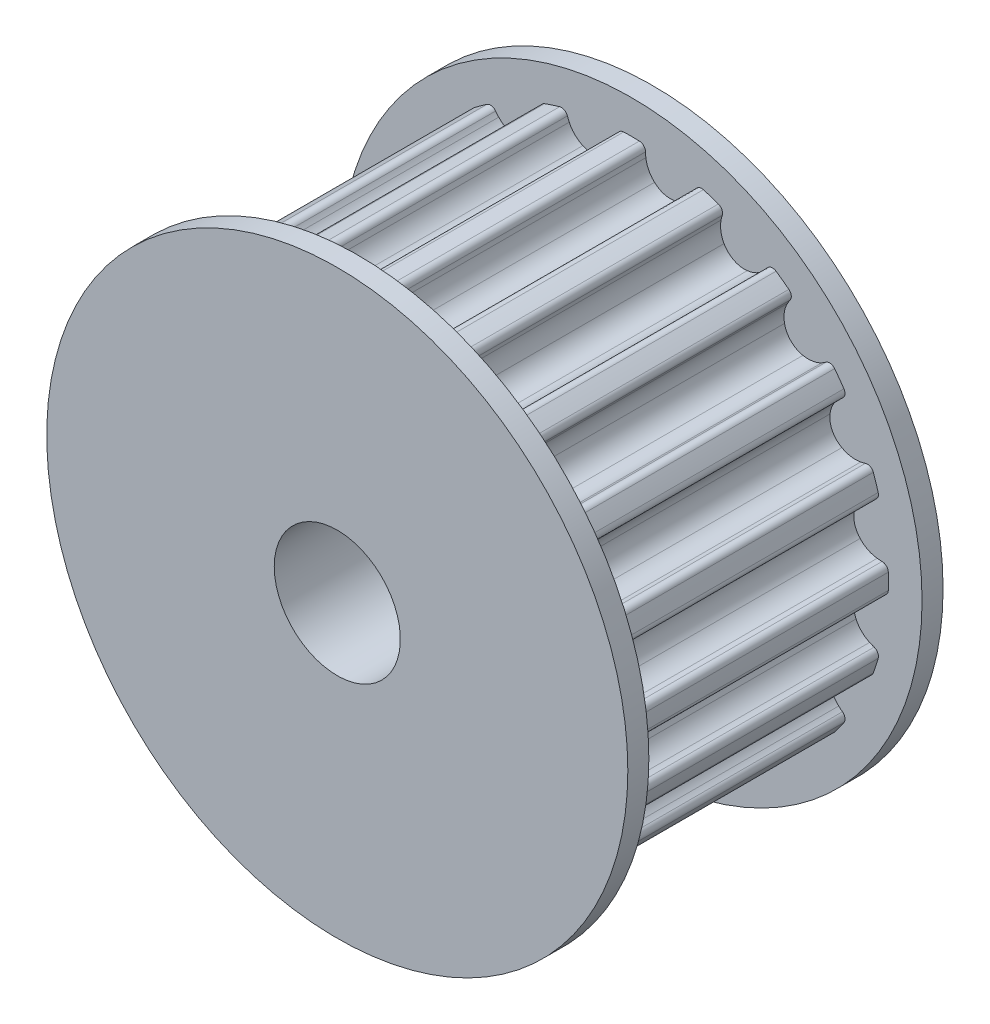
SolidWorks part; units mm, degrees
material "PET"
ref_plane "Front Plane" through (0, 0, 0) normal (0, 0, 1) x (1, 0, 0)
ref_plane "Top Plane" through (0, 0, 0) normal (0, 1, 0) x (1, 0, 0)
ref_plane "Right Plane" through (0, 0, 0) normal (1, 0, 0) x (0, 0, -1)
sketch "Sketch1" plane through (0, 0, 0) normal (0, 0, 1) x (1, 0, 0)
  line L0 (0, 0) -> (0, 6.3662) construction
  line L1 (0, 0) -> (0.9959, 6.2878) construction
  line L2 (0, 0) -> (1.3887, 6.2129) construction
  circle A0 centre (0, 0) radius 6.3662 construction
  circle A1 centre (0, 0) radius 5.3622 construction
  circle A2 centre (0, 0) radius 6.1122 construction
  arc A3 (0.8388, 5.2962) -> (0.5472, 5.4384) centre (0.9257, 5.8443) cw
  arc A4 (0.3406, 5.8443) -> (0.3333, 5.9601) centre (1.3333, 5.965) cw
  circle A5 centre (0, 0) radius 5.9622 construction
  arc A6 (-0.188, 6.1093) -> (0.188, 6.1093) centre (0, 0) cw
  arc A7 (0.188, 6.1093) -> (0.3333, 5.9601) centre (0.1833, 5.9594) cw
  arc A8 (0.3406, 5.8443) -> (0.5472, 5.4384) centre (1.0004, 5.9245) ccw
  arc A9 (-0.8388, 5.2962) -> (-0.5472, 5.4384) centre (-0.9257, 5.8443) ccw
  arc A10 (-0.3406, 5.8443) -> (-0.5472, 5.4384) centre (-1.0004, 5.9245) cw
  arc A11 (-0.3406, 5.8443) -> (-0.3333, 5.9601) centre (-1.3333, 5.965) ccw
  arc A12 (-0.188, 6.1093) -> (-0.3333, 5.9601) centre (-0.1833, 5.9594) ccw
  arc A13 (-0.8388, 5.2962) -> (0.8388, 5.2962) centre (0, 0) cw
  dimension "D1" = 12.7324
  dimension "D6" = 0.555
  dimension "D7" = 1
  dimension "D9" = 0.15
  dimension "D2" = 9
  dimension "D3" = 3.6
  dimension "D4" = 1.004
  dimension "D5" = 0.75
  dimension "D8" = 0.15
extrude "Boss-Extrude1" add sketch "Sketch1" along normal blind 6.5
ref_axis "Axis1" through (0, 0, -0.375) along (0, 0, 1)
pattern_circular "CirPattern1" count 20 over 360 about axis through (0, 0, -0.375) along (0, 0, 1) of bodies 107
sketch "Sketch2" plane through (0, 0, 0) normal (0, 0, -1) x (-1, 0, 0)
  circle A0 centre (0, 0) radius 5.3622
  arc A1 (0.8388, 5.2962) -> (-0.8388, 5.2962) centre (0, 0) ccw construction
extrude "Boss-Extrude2" add sketch "Sketch2" against normal up to surface (6.5 mm away)
sketch "Schizzo1" plane through (0, 0, 6.5) normal (0, 0, 1) x (1, 0, 0)
  circle A0 centre (0, 0) radius 6.9122
  arc A1 (-6.1093, 0.188) -> (-6.1093, -0.188) centre (0, 0) ccw construction
  dimension "D1" = 0.8
extrude "Estrusione-Estrusione1" add sketch "Schizzo1" along normal blind 0.5
ref_plane "Piano1" through (0, 0, 3.25) normal (0, 0, -1) x (-1, 0, 0)
mirror "Specchia1" about plane through (0, 0, 3.25) normal (0, 0, -1) of "Estrusione-Estrusione1"
sketch "Schizzo3" plane through (0, 0, -0.5) normal (0, 0, -1) x (-1, 0, 0)
  circle A0 centre (0, 0) radius 1.5
  dimension "D1" = 3
extrude "Taglio-Estrusione2" cut sketch "Schizzo3" against normal through all
sketch "Schizzo2" plane through (0, 0, -0.5) normal (0, 0, -1) x (-1, 0, 0)
  arc A0 (-0.1172, 3.5721) -> (-0.645, 4.6555) centre (-1.906, 3.3711) ccw
  arc A1 (0.1172, 3.5721) -> (-0.1172, 3.5721) centre (0, 0) ccw
  arc A2 (0.645, 4.6555) -> (0.1172, 3.5721) centre (1.906, 3.3711) ccw
  arc A3 (1.1857, 4.548) -> (0.645, 4.6555) centre (0, 0) ccw
  arc A4 (1.2587, 3.345) -> (1.1857, 4.548) centre (-0.4708, 3.8439) ccw
  arc A5 (1.4753, 3.2553) -> (1.2587, 3.345) centre (0, 0) ccw
  arc A6 (2.3775, 4.0543) -> (1.4753, 3.2553) centre (3.051, 2.3851) ccw
  arc A7 (2.8359, 3.748) -> (2.3775, 4.0543) centre (0, 0) ccw
  arc A8 (2.4429, 2.6087) -> (2.8359, 3.748) centre (1.036, 3.7314) ccw
  arc A9 (2.6087, 2.4429) -> (2.4429, 2.6087) centre (0, 0) ccw
  arc A10 (3.748, 2.8359) -> (2.6087, 2.4429) centre (3.7314, 1.036) ccw
  arc A11 (4.0543, 2.3775) -> (3.748, 2.8359) centre (0, 0) ccw
  arc A12 (3.2553, 1.4753) -> (4.0543, 2.3775) centre (2.3851, 3.051) ccw
  arc A13 (3.345, 1.2587) -> (3.2553, 1.4753) centre (0, 0) ccw
  arc A14 (4.548, 1.1857) -> (3.345, 1.2587) centre (3.8439, -0.4708) ccw
  arc A15 (4.6555, 0.645) -> (4.548, 1.1857) centre (0, 0) ccw
  arc A16 (3.5721, 0.1172) -> (4.6555, 0.645) centre (3.3711, 1.906) ccw
  arc A17 (3.5721, -0.1172) -> (3.5721, 0.1172) centre (0, 0) ccw
  arc A18 (4.6555, -0.645) -> (3.5721, -0.1172) centre (3.3711, -1.906) ccw
  arc A19 (4.548, -1.1857) -> (4.6555, -0.645) centre (0, 0) ccw
  arc A20 (3.345, -1.2587) -> (4.548, -1.1857) centre (3.8439, 0.4708) ccw
  arc A21 (3.2553, -1.4753) -> (3.345, -1.2587) centre (0, 0) ccw
  arc A22 (4.0543, -2.3775) -> (3.2553, -1.4753) centre (2.3851, -3.051) ccw
  arc A23 (3.748, -2.8359) -> (4.0543, -2.3775) centre (0, 0) ccw
  arc A24 (2.6087, -2.4429) -> (3.748, -2.8359) centre (3.7314, -1.036) ccw
  arc A25 (2.4429, -2.6087) -> (2.6087, -2.4429) centre (0, 0) ccw
  arc A26 (2.8359, -3.748) -> (2.4429, -2.6087) centre (1.036, -3.7314) ccw
  arc A27 (2.3775, -4.0543) -> (2.8359, -3.748) centre (0, 0) ccw
  arc A28 (1.4753, -3.2553) -> (2.3775, -4.0543) centre (3.051, -2.3851) ccw
  arc A29 (1.2587, -3.345) -> (1.4753, -3.2553) centre (0, 0) ccw
  arc A30 (1.1857, -4.548) -> (1.2587, -3.345) centre (-0.4708, -3.8439) ccw
  arc A31 (0.645, -4.6555) -> (1.1857, -4.548) centre (0, 0) ccw
  arc A32 (0.1172, -3.5721) -> (0.645, -4.6555) centre (1.906, -3.3711) ccw
  arc A33 (-0.1172, -3.5721) -> (0.1172, -3.5721) centre (0, 0) ccw
  arc A34 (-0.645, -4.6555) -> (-0.1172, -3.5721) centre (-1.906, -3.3711) ccw
  arc A35 (-1.1857, -4.548) -> (-0.645, -4.6555) centre (0, 0) ccw
  arc A36 (-1.2587, -3.345) -> (-1.1857, -4.548) centre (0.4708, -3.8439) ccw
  arc A37 (-1.4753, -3.2553) -> (-1.2587, -3.345) centre (0, 0) ccw
  arc A38 (-2.3775, -4.0543) -> (-1.4753, -3.2553) centre (-3.051, -2.3851) ccw
  arc A39 (-2.8359, -3.748) -> (-2.3775, -4.0543) centre (0, 0) ccw
  arc A40 (-2.4429, -2.6087) -> (-2.8359, -3.748) centre (-1.036, -3.7314) ccw
  arc A41 (-2.6087, -2.4429) -> (-2.4429, -2.6087) centre (0, 0) ccw
  arc A42 (-3.748, -2.8359) -> (-2.6087, -2.4429) centre (-3.7314, -1.036) ccw
  arc A43 (-4.0543, -2.3775) -> (-3.748, -2.8359) centre (0, 0) ccw
  arc A44 (-3.2553, -1.4753) -> (-4.0543, -2.3775) centre (-2.3851, -3.051) ccw
  arc A45 (-3.345, -1.2587) -> (-3.2553, -1.4753) centre (0, 0) ccw
  arc A46 (-4.548, -1.1857) -> (-3.345, -1.2587) centre (-3.8439, 0.4708) ccw
  arc A47 (-4.6555, -0.645) -> (-4.548, -1.1857) centre (0, 0) ccw
  arc A48 (-3.5721, -0.1172) -> (-4.6555, -0.645) centre (-3.3711, -1.906) ccw
  arc A49 (-3.5721, 0.1172) -> (-3.5721, -0.1172) centre (0, 0) ccw
  arc A50 (-4.6555, 0.645) -> (-3.5721, 0.1172) centre (-3.3711, 1.906) ccw
  arc A51 (-4.548, 1.1857) -> (-4.6555, 0.645) centre (0, 0) ccw
  arc A52 (-3.345, 1.2587) -> (-4.548, 1.1857) centre (-3.8439, -0.4708) ccw
  arc A53 (-3.2553, 1.4753) -> (-3.345, 1.2587) centre (0, 0) ccw
  arc A54 (-4.0543, 2.3775) -> (-3.2553, 1.4753) centre (-2.3851, 3.051) ccw
  arc A55 (-3.748, 2.8359) -> (-4.0543, 2.3775) centre (0, 0) ccw
  arc A56 (-2.6087, 2.4429) -> (-3.748, 2.8359) centre (-3.7314, 1.036) ccw
  arc A57 (-2.4429, 2.6087) -> (-2.6087, 2.4429) centre (0, 0) ccw
  arc A58 (-2.8359, 3.748) -> (-2.4429, 2.6087) centre (-1.036, 3.7314) ccw
  arc A59 (-2.3775, 4.0543) -> (-2.8359, 3.748) centre (0, 0) ccw
  arc A60 (-1.4753, 3.2553) -> (-2.3775, 4.0543) centre (-3.051, 2.3851) ccw
  arc A61 (-1.2587, 3.345) -> (-1.4753, 3.2553) centre (0, 0) ccw
  arc A62 (-1.1857, 4.548) -> (-1.2587, 3.345) centre (0.4708, 3.8439) ccw
  arc A63 (-0.645, 4.6555) -> (-1.1857, 4.548) centre (0, 0) ccw
  arc A64 (-0.2087, 3.4677) -> (-0.6806, 4.5494) centre (-1.906, 3.3711) ccw
  arc A65 (-0.6806, 4.5494) -> (-1.1122, 4.4635) centre (0, 0) ccw
  arc A66 (-1.1122, 4.4635) -> (-1.1342, 3.2836) centre (0.4708, 3.8439) ccw
  arc A67 (-1.1342, 3.2836) -> (-1.5199, 3.1239) centre (0, 0) ccw
  arc A68 (-1.5199, 3.1239) -> (-2.3697, 3.9426) centre (-3.051, 2.3851) ccw
  arc A69 (-2.3697, 3.9426) -> (-2.7356, 3.6981) centre (0, 0) ccw
  arc A70 (-2.7356, 3.6981) -> (-2.3045, 2.5997) centre (-1.036, 3.7314) ccw
  arc A71 (-2.3045, 2.5997) -> (-2.5997, 2.3045) centre (0, 0) ccw
  arc A72 (-2.5997, 2.3045) -> (-3.6981, 2.7356) centre (-3.7314, 1.036) ccw
  arc A73 (-3.6981, 2.7356) -> (-3.9426, 2.3697) centre (0, 0) ccw
  arc A74 (-3.9426, 2.3697) -> (-3.1239, 1.5199) centre (-2.3851, 3.051) ccw
  arc A75 (-3.1239, 1.5199) -> (-3.2836, 1.1342) centre (0, 0) ccw
  arc A76 (-3.2836, 1.1342) -> (-4.4635, 1.1122) centre (-3.8439, -0.4708) ccw
  arc A77 (-4.4635, 1.1122) -> (-4.5494, 0.6806) centre (0, 0) ccw
  arc A78 (-4.5494, 0.6806) -> (-3.4677, 0.2087) centre (-3.3711, 1.906) ccw
  arc A79 (-3.4677, 0.2087) -> (-3.4677, -0.2087) centre (0, 0) ccw
  arc A80 (-3.4677, -0.2087) -> (-4.5494, -0.6806) centre (-3.3711, -1.906) ccw
  arc A81 (-4.5494, -0.6806) -> (-4.4635, -1.1122) centre (0, 0) ccw
  arc A82 (-4.4635, -1.1122) -> (-3.2836, -1.1342) centre (-3.8439, 0.4708) ccw
  arc A83 (-3.2836, -1.1342) -> (-3.1239, -1.5199) centre (0, 0) ccw
  arc A84 (-3.1239, -1.5199) -> (-3.9426, -2.3697) centre (-2.3851, -3.051) ccw
  arc A85 (-3.9426, -2.3697) -> (-3.6981, -2.7356) centre (0, 0) ccw
  arc A86 (-3.6981, -2.7356) -> (-2.5997, -2.3045) centre (-3.7314, -1.036) ccw
  arc A87 (-2.5997, -2.3045) -> (-2.3045, -2.5997) centre (0, 0) ccw
  arc A88 (-2.3045, -2.5997) -> (-2.7356, -3.6981) centre (-1.036, -3.7314) ccw
  arc A89 (-2.7356, -3.6981) -> (-2.3697, -3.9426) centre (0, 0) ccw
  arc A90 (-2.3697, -3.9426) -> (-1.5199, -3.1239) centre (-3.051, -2.3851) ccw
  arc A91 (-1.5199, -3.1239) -> (-1.1342, -3.2836) centre (0, 0) ccw
  arc A92 (-1.1342, -3.2836) -> (-1.1122, -4.4635) centre (0.4708, -3.8439) ccw
  arc A93 (-1.1122, -4.4635) -> (-0.6806, -4.5494) centre (0, 0) ccw
  arc A94 (-0.6806, -4.5494) -> (-0.2087, -3.4677) centre (-1.906, -3.3711) ccw
  arc A95 (-0.2087, -3.4677) -> (0.2087, -3.4677) centre (0, 0) ccw
  arc A96 (0.2087, -3.4677) -> (0.6806, -4.5494) centre (1.906, -3.3711) ccw
  arc A97 (0.6806, -4.5494) -> (1.1122, -4.4635) centre (0, 0) ccw
  arc A98 (1.1122, -4.4635) -> (1.1342, -3.2836) centre (-0.4708, -3.8439) ccw
  arc A99 (1.1342, -3.2836) -> (1.5199, -3.1239) centre (0, 0) ccw
  arc A100 (1.5199, -3.1239) -> (2.3697, -3.9426) centre (3.051, -2.3851) ccw
  arc A101 (2.3697, -3.9426) -> (2.7356, -3.6981) centre (0, 0) ccw
  arc A102 (2.7356, -3.6981) -> (2.3045, -2.5997) centre (1.036, -3.7314) ccw
  arc A103 (2.3045, -2.5997) -> (2.5997, -2.3045) centre (0, 0) ccw
  arc A104 (2.5997, -2.3045) -> (3.6981, -2.7356) centre (3.7314, -1.036) ccw
  arc A105 (3.6981, -2.7356) -> (3.9426, -2.3697) centre (0, 0) ccw
  arc A106 (3.9426, -2.3697) -> (3.1239, -1.5199) centre (2.3851, -3.051) ccw
  arc A107 (3.1239, -1.5199) -> (3.2836, -1.1342) centre (0, 0) ccw
  arc A108 (3.2836, -1.1342) -> (4.4635, -1.1122) centre (3.8439, 0.4708) ccw
  arc A109 (4.4635, -1.1122) -> (4.5494, -0.6806) centre (0, 0) ccw
  arc A110 (4.5494, -0.6806) -> (3.4677, -0.2087) centre (3.3711, -1.906) ccw
  arc A111 (3.4677, -0.2087) -> (3.4677, 0.2087) centre (0, 0) ccw
  arc A112 (3.4677, 0.2087) -> (4.5494, 0.6806) centre (3.3711, 1.906) ccw
  arc A113 (4.5494, 0.6806) -> (4.4635, 1.1122) centre (0, 0) ccw
  arc A114 (4.4635, 1.1122) -> (3.2836, 1.1342) centre (3.8439, -0.4708) ccw
  arc A115 (3.2836, 1.1342) -> (3.1239, 1.5199) centre (0, 0) ccw
  arc A116 (3.1239, 1.5199) -> (3.9426, 2.3697) centre (2.3851, 3.051) ccw
  arc A117 (3.9426, 2.3697) -> (3.6981, 2.7356) centre (0, 0) ccw
  arc A118 (3.6981, 2.7356) -> (2.5997, 2.3045) centre (3.7314, 1.036) ccw
  arc A119 (2.5997, 2.3045) -> (2.3045, 2.5997) centre (0, 0) ccw
  arc A120 (2.3045, 2.5997) -> (2.7356, 3.6981) centre (1.036, 3.7314) ccw
  arc A121 (2.7356, 3.6981) -> (2.3697, 3.9426) centre (0, 0) ccw
  arc A122 (2.3697, 3.9426) -> (1.5199, 3.1239) centre (3.051, 2.3851) ccw
  arc A123 (1.5199, 3.1239) -> (1.1342, 3.2836) centre (0, 0) ccw
  arc A124 (1.1342, 3.2836) -> (1.1122, 4.4635) centre (-0.4708, 3.8439) ccw
  arc A125 (1.1122, 4.4635) -> (0.6806, 4.5494) centre (0, 0) ccw
  arc A126 (0.6806, 4.5494) -> (0.2087, 3.4677) centre (1.906, 3.3711) ccw
  arc A127 (0.2087, 3.4677) -> (-0.2087, 3.4677) centre (0, 0) ccw
  point P128 (0, 0)
  dimension "D1" = 0.1
extrude "Taglio-Estrusione1" cut sketch "Schizzo2" against normal blind 5.1 contours A64 A65 A66 A67 A68 A69 A70 A71 A72 A73 A74 A75 A76 A77 A78 A79 A80 A81 A82 A83 A84 A85 A86 A87 A88 A89 A90 A91 A92 A93 A94 A95 A96 A97 A98 A99 A100 A101 A102 A103 A104 A105 A106 A107 A108 A109 A110 A111 A112 A113 A114 A115 A116 A117 A118 A119 A120 A121 A122 A123 A124 A125 A126 A127
equation "\"NumTeeth\"= 20'The number of teeth that the pulley has"
equation "\"ToothPitch\"= 2.00mm'Distance between 2 teeth"
equation "\"PulleyDia\"= \"NumTeeth\" * \"ToothPitch\" / PI"
equation "\"ToothAng\"= ( 360deg / \"NumTeeth\" ) * 1deg"
equation "\"TransOffsetAngle\"= \"ToothAng\" * .2deg"
equation "\"ShoulderRad\"= 0.15mm"
equation "\"RootRad\"= 0.555mm"
equation "\"TransRad\"= 1mm"
equation "\"ToothHeight\"= 0.75mm"
equation "\"PLD\"= 0.254mm"
equation "\"D1@CirPattern1\"=\"NumTeeth\""
equation "\"D1@Sketch1\"=\"PulleyDia\""
equation "\"D7@Sketch1\"=\"TransRad\""
equation "\"D9@Sketch1\"=\"ShoulderRad\""
equation "\"D6@Sketch1\"=\"RootRad\""
equation "\"D3@Sketch1\"=\"TransOffsetAngle\""
equation "\"D5@Sketch1\"=\"ToothHeight\""
equation "\"D2@Sketch1\"=\"ToothAng\"/2"
equation "\"D4@Sketch1\"=\"PLD\"+\"ToothHeight\""
equation "\"D8@Sketch1\"=\"ShoulderRad\""
equation "\"altezza\"= 6.5mm"
equation "\"D1@Boss-Extrude1\"=\"altezza\""
